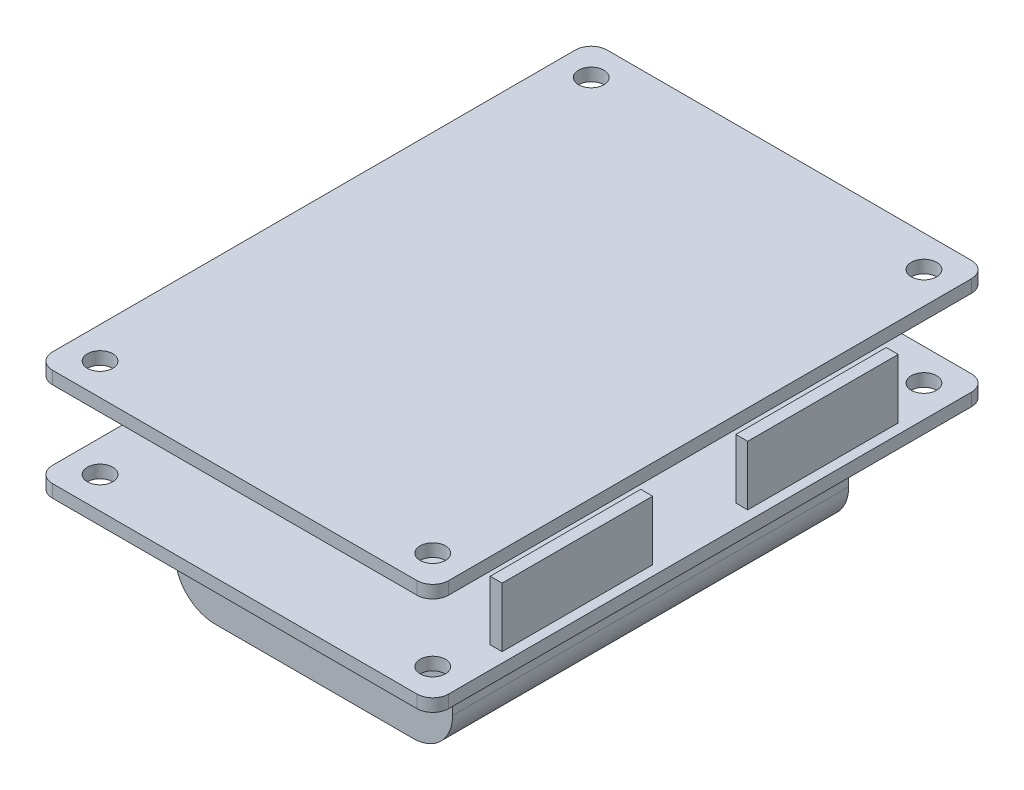
SolidWorks part; units mm, degrees
ref_plane "Front Plane" through (0, 0, 0) normal (0, 0, 1) x (1, 0, 0)
ref_plane "Top Plane" through (0, 0, 0) normal (0, 1, 0) x (1, 0, 0)
ref_plane "Right Plane" through (0, 0, 0) normal (1, 0, 0) x (0, 0, -1)
sketch "Sketch1" plane through (0, 0, 0) normal (0, 1, 0) x (1, 0, 0)
  line L1 (-25, -35) -> (25, -35)
  line L2 (-25, -35) -> (-25, 35)
  line L3 (-25, 35) -> (25, 35)
  line L4 (25, -35) -> (25, 35)
  line L5 (-25, -35) -> (25, 35) construction
  line L6 (-25, 35) -> (25, -35) construction
  line L7 (-21, 31) -> (21, 31)
  line L8 (-21, 31) -> (-21, -31)
  line L9 (-21, -31) -> (21, -31)
  line L10 (21, 31) -> (21, -31)
  circle A0 centre (-21, 31) radius 1.6
  circle A1 centre (21, 31) radius 1.6
  circle A2 centre (-21, -31) radius 1.6
  circle A3 centre (21, -31) radius 1.6
  point P0 (0, 0)
  point P8 (0, 31)
  point P17 (-21, 0)
  dimension "D3" = 3.2
  dimension "D1" = 50
  dimension "D2" = 70
  dimension "D4" = 4
  dimension "D5" = 4
extrude "Boss-Extrude1" add sketch "Sketch1" along normal mid plane 1.6 contours L2 L3 L4 L1 | A0 | A1 | A3 | A2
extrude "GPS extension Module" add sketch "Sketch1<3>" along normal blind 1.6 from offset 11.6 separate body contours L2 L3 L4 L1 | A2 | A3 | A1 | A0
sketch "Sketch1<3>" plane through (0, 0, 0) normal (0, 1, 0) x (1, 0, 0) same geometry as "Sketch1"
sketch "Sketch2" plane through (0, 0.8, 0) normal (0, 1, 0) x (1, 0, 0)
  line L0 (-25, 35) -> (25, 35) construction
  line L1 (23.75, 25) -> (22.25, 25)
  line L2 (23.75, 25) -> (23.75, -25)
  line L3 (23.75, -25) -> (22.25, -25)
  line L4 (22.25, 25) -> (22.25, -25)
  line L5 (25, -35) -> (25, 35) construction
  line L6 (22.25, 6) -> (23.75, 6)
  line L7 (22.25, 6) -> (22.25, -6)
  line L8 (22.25, -6) -> (23.75, -6)
  line L9 (23.75, 6) -> (23.75, -6)
  point P6 (22.25, 0)
  point P12 (22.25, 0)
  point P19 (23, 6)
  dimension "D1" = 10
  dimension "D2" = 12
  dimension "D3" = 1.5
  dimension "D4" = 2
extrude "Headers" add sketch "Sketch2" along normal blind 7.5 contours L4 L6 L2 L1 | L8 L4 L3 L2 region at (23, 0.8, -15.5) region at (23, 0.8, 15.5)
sketch "Sketch3" plane through (0, -0.8, 0) normal (0, -1, 0) x (1, 0, 0)
  line L1 (-17.5, -25) -> (17.5, -25)
  line L2 (-17.5, -25) -> (-17.5, 25)
  line L3 (-17.5, 25) -> (17.5, 25)
  line L4 (17.5, -25) -> (17.5, 25)
  line L5 (-17.5, -25) -> (17.5, 25) construction
  line L6 (-17.5, 25) -> (17.5, -25) construction
  point P0 (0, 0)
  dimension "D1" = 35
  dimension "D2" = 50
extrude "Batteries" add sketch "Sketch3" along normal blind 13.5
fillet "Fillet1" radius 2 4 edges at (-25, 0, -35) (25, 0, -35) (25, 0, 35) (-25, 0, 35)
fillet "Fillet2" radius 5 2 edges at (-17.5, -14.3, 0) (17.5, -14.3, 0)
fillet "Fillet3" radius 2 4 edges at (-25, 12.4, -35) (25, 12.4, -35) (25, 12.4, 35) (-25, 12.4, 35)
